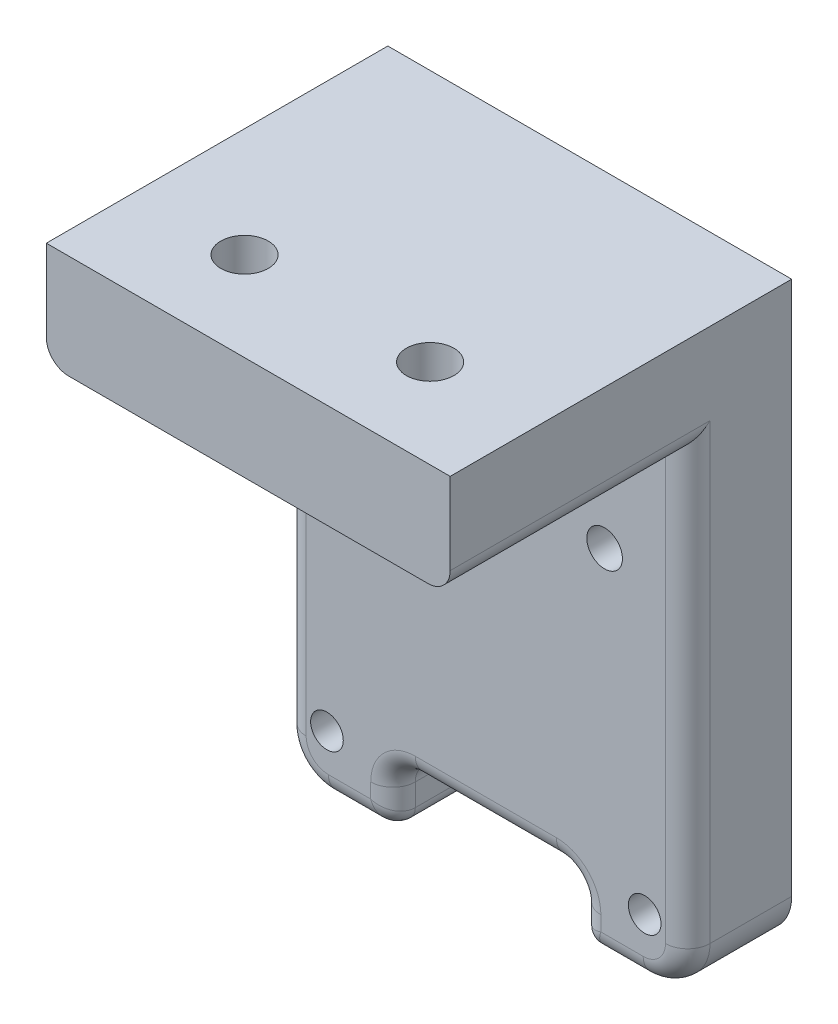
SolidWorks part; units mm, degrees
ref_plane "Front Plane" through (0, 0, 0) normal (0, 0, 1) x (1, 0, 0)
ref_plane "Top Plane" through (0, 0, 0) normal (0, 1, 0) x (1, 0, 0)
ref_plane "Right Plane" through (0, 0, 0) normal (1, 0, 0) x (0, 0, -1)
sketch "Sketch1" plane through (0, 0, 0) normal (0, 0, 1) x (1, 0, 0)
  line L0 (-10.7, 0) -> (10.7, 0) construction
  line L1 (-13.6, 4) -> (-13.6, 28)
  line L6 (-13.6, 4) -> (13.6, 4) construction
  line L7 (-13.6, 4) -> (-13.6, -1)
  line L12 (-10.6, -4) -> (-7.25, -4)
  line L13 (13.6, 4) -> (13.6, -1)
  line L14 (-13.6, 4) -> (13.6, -4) construction
  line L15 (-13.6, -4) -> (13.6, 4) construction
  line L16 (-13.6, 28) -> (13.6, 28)
  line L17 (13.6, 28) -> (13.6, 4)
  line L18 (-6.25, -3) -> (-6.25, -1.5)
  line L19 (-4.75, 0) -> (4.75, 0)
  line L20 (6.25, -1.5) -> (6.25, -3)
  line L21 (7.25, -4) -> (10.6, -4)
  circle A0 centre (-10.7, 0) radius 1.1
  circle A1 centre (10.7, 0) radius 1.1
  arc A2 (10.6, -4) -> (13.6, -1) centre (10.6, -1) ccw
  arc A3 (-13.6, -1) -> (-10.6, -4) centre (-10.6, -1) ccw
  arc A4 (4.75, 0) -> (6.25, -1.5) centre (4.75, -1.5) cw
  arc A5 (-6.25, -1.5) -> (-4.75, 0) centre (-4.75, -1.5) cw
  arc A6 (6.25, -3) -> (7.25, -4) centre (7.25, -3) ccw
  arc A7 (-6.25, -3) -> (-7.25, -4) centre (-7.25, -3) cw
  point P4 (0, 0)
  point P7 (0, 1.4865)
  point P8 (0, 0)
  point P13 (0, -1.35)
  point P25 (0, 0)
  point P29 (6.25, 0)
  point P32 (-6.25, 0)
  point P35 (6.25, -4)
  dimension "D2" = 2.2
  dimension "D7" = 12.5
  dimension "D5" = 3
  dimension "D8" = 1.5
  dimension "D9" = 1
  dimension "D1" = 21.4
  dimension "D3" = 27.2
  dimension "D4" = 8
  dimension "D6" = 28
extrude "Boss-Extrude1" add sketch "Sketch1" along normal blind 7
sketch "Sketch2" plane through (0, 0, 0) normal (0, 0, 1) x (1, 0, 0)
  line L0 (13.6, 28) -> (-13.6, 28) construction
  line L1 (13.6, 28) -> (-13.6, 28)
  line L2 (-13.6, 28) -> (-13.6, 35)
  line L3 (-13.6, 35) -> (13.6, 35)
  line L4 (13.6, 35) -> (13.6, 28)
  point P3 (13.6, 31.9032)
  dimension "D1" = 7
extrude "Boss-Extrude2" add sketch "Sketch2" along normal blind 23
sketch "Sketch4" plane through (0, 35, 0) normal (0, 1, 0) x (1, 0, 0)
  line L0 (6.25, -17) -> (-6.25, -17) construction
  line L1 (13.6, 0) -> (-13.6, 0) construction
  circle A0 centre (6.25, -17) radius 1.6
  circle A1 centre (-6.25, -17) radius 1.6
  point P0 (9.2223, -17)
  point P4 (0, 0)
  point P5 (0, 0)
  point P7 (0, -17)
  dimension "D2" = 3.2
  dimension "D1" = 17
  dimension "D3" = 12.5
extrude "Cut-Extrude1" cut sketch "Sketch4" against normal up to next
sketch "Sketch5" plane through (0, 21, 7) normal (0, 0, 1) x (1, 0, 0)
  line L0 (8, -1) -> (-8, -1) construction
  line L2 (13.6, 7) -> (-13.6, 7) construction
  circle A0 centre (-8, -1) radius 1.2
  circle A1 centre (8, -1) radius 1.2
  point P2 (0, 0)
  point P4 (0, 0)
  point P5 (0, 0.2587)
  point P7 (0, -1)
  point P9 (0, 0.6388)
  dimension "D2" = 2.4
  dimension "D1" = 16
  dimension "D3" = 8
extrude "Cut-Extrude2" cut sketch "Sketch5" against normal up to next
fillet "Fillet1" radius 1.5 15 edges at (13.6, 13.5, 7) (-8.925, -4, 7) (-13.6, 13.5, 7) (-13.6, 28, 15) (13.6, 28, 15) (12.7213, -3.1213, 7) (-12.7213, -3.1213, 7) (8.925, -4, 7) (6.5429, -3.7071, 7) (6.25, -2.25, 7) (5.8107, -0.4393, 7) (0, 0, 7) (-5.8107, -0.4393, 7) (-6.25, -2.25, 7) (-6.5429, -3.7071, 7)
